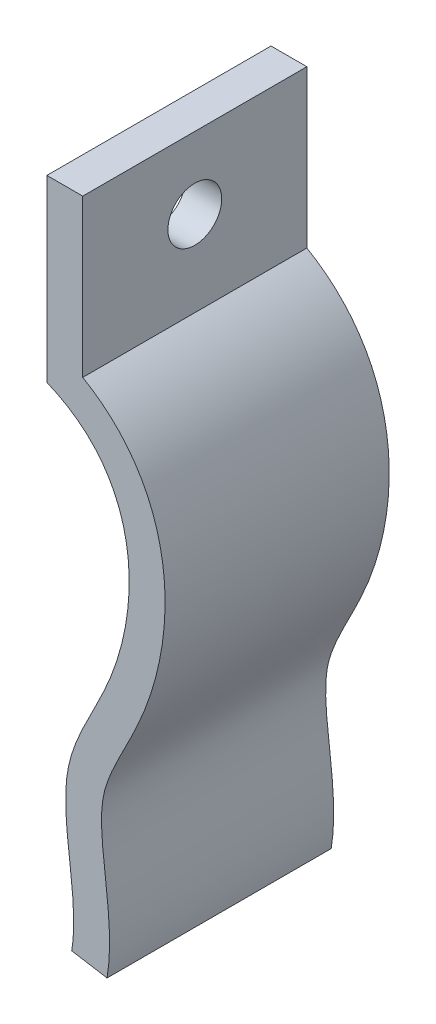
SolidWorks part; units mm, degrees
ref_plane "Ön Düzlem" through (0, 0, 0) normal (0, 0, 1) x (1, 0, 0)
ref_plane "Üst Düzlem" through (0, 0, 0) normal (0, 1, 0) x (1, 0, 0)
ref_plane "Sağ Düzlem" through (0, 0, 0) normal (1, 0, 0) x (0, 0, -1)
sketch "Çizim1" plane through (0, 0, 0) normal (0, 0, 1) x (1, 0, 0)
  line L0 (0, 41.8099) -> (0, 21.8099)
  line L1 (4, 41.8099) -> (4, 24.2964)
  line L2 (0, 41.8099) -> (4, 41.8099)
  line L3 (2.7684, -31.7069) -> (6.7145, -32.3612)
  spline S0 degree 3 poles (0, 21.8099) (10.5687, 17.4853) (10.8615, 0.8206) (0.9983, -13.7254) (2.7959, -23.6402) (3.1211, -29.5799) (2.7684, -31.7069) knots 0 0 0 0 0.502232 0.695448 0.885833 1 1 1 1
  spline S1 degree 1 poles (4, 24.2964) (6.7145, -32.3612) knots 0 0 1 1 construction
  spline S2 degree 3 poles (4, 24.2964) (4.6852, 23.9004) (6.022, 23.0113) (8.3339, 20.9926) (10.609, 18.0309) (12.3264, 14.0662) (13.1595, 9.9108) (13.2499, 5.7018) (12.7186, 1.5308) (11.8331, -1.8486) (10.899, -4.4521) (9.8104, -6.9845) (8.3727, -9.7588) (7.2043, -12.1465) (6.5751, -13.8552) (6.2779, -15.001) (6.1214, -16.211) (6.0652, -18.048) (6.2666, -20.675) (6.7224, -24.2353) (7.0119, -27.48) (6.9828, -30.2151) (6.8312, -31.6574) (6.7145, -32.3612) knots 0.033865 0.033865 0.033865 0.033865 0.064056 0.094248 0.154631 0.215015 0.275398 0.335782 0.396165 0.456549 0.486741 0.516932 0.577316 0.637699 0.667891 0.698083 0.728274 0.758466 0.81885 0.879233 0.939617 0.969808 1 1 1 1
  dimension "D2" = 20
  dimension "D1" = 4
extrude "Yükseklik-Ekstrüzyon1" add sketch "Çizim1" along normal blind 25
sketch "Çizim2" plane through (4, 0, 0) normal (1, 0, 0) x (0, 0, -1)
  line L0 (-25, 24.2964) -> (-25, 41.8099) construction
  line L1 (-25, 41.8099) -> (0, 41.8099) construction
  circle A0 centre (-12.5, 33.8099) radius 3
  dimension "D1" = 12.5
  dimension "D2" = 8
extrude "Kes-Ekstrüzyon1" cut sketch "Çizim2" against normal blind 25
